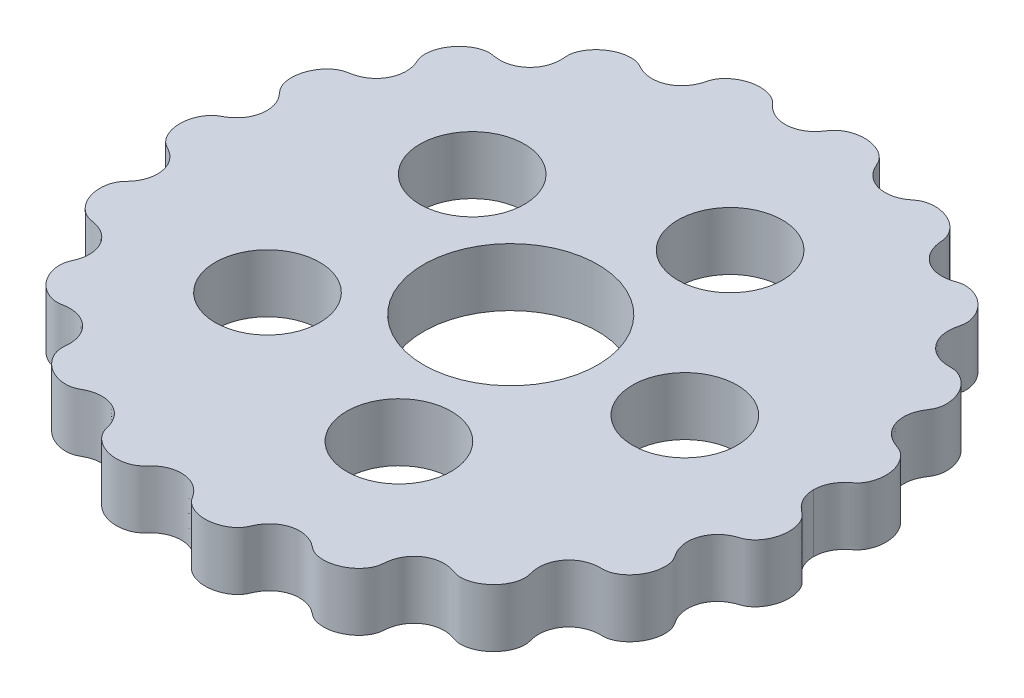
SolidWorks part; units mm, degrees
ref_plane "Front Plane" through (0, 0, 0) normal (0, 0, 1) x (1, 0, 0)
ref_plane "Top Plane" through (0, 0, 0) normal (0, 1, 0) x (1, 0, 0)
ref_plane "Right Plane" through (0, 0, 0) normal (1, 0, 0) x (0, 0, -1)
sketch "Sketch1" plane through (0, 0, 0) normal (0, 1, 0) x (1, 0, 0)
  line L0 (-28.5, 0) -> (26.1, 0) construction
  line L1 (0, 0) -> (-1.2, 0) construction
  line L2 (-1.2, -26.2965) -> (-1.2, 26.2965) construction
  line L3 (0, -27.4748) -> (0, 27.4748) construction
  line L4 (15, 0) -> (16.8, 0)
  line L5 (-1.2, 0) -> (-2.4, 0)
  circle A6 centre (0, 0) radius 7.5
  circle A7 centre (0, 0) radius 15
  circle A8 centre (15, 0) radius 4.5
  circle A9 centre (4.6353, -14.2658) radius 4.5
  circle A10 centre (-12.1353, -8.8168) radius 4.5
  circle A11 centre (-12.1353, 8.8168) radius 4.5
  circle A12 centre (4.6353, 14.2658) radius 4.5
  circle A13 centre (-1.2, 0) radius 30
  circle A14 centre (28.8, 0) radius 2.5
  circle A15 centre (27.3317, -9.2705) radius 2.5
  circle A16 centre (23.0705, -17.6336) radius 2.5
  circle A17 centre (16.4336, -24.2705) radius 2.5
  circle A18 centre (8.0705, -28.5317) radius 2.5
  circle A19 centre (-1.2, -30) radius 2.5
  circle A20 centre (-10.4705, -28.5317) radius 2.5
  circle A21 centre (-18.8336, -24.2705) radius 2.5
  circle A22 centre (-25.4705, -17.6336) radius 2.5
  circle A23 centre (-29.7317, -9.2705) radius 2.5
  circle A24 centre (-31.2, 0) radius 2.5
  circle A25 centre (-29.7317, 9.2705) radius 2.5
  circle A26 centre (-25.4705, 17.6336) radius 2.5
  circle A27 centre (-18.8336, 24.2705) radius 2.5
  circle A28 centre (-10.4705, 28.5317) radius 2.5
  circle A29 centre (-1.2, 30) radius 2.5
  circle A30 centre (8.0705, 28.5317) radius 2.5
  circle A31 centre (16.4336, 24.2705) radius 2.5
  circle A32 centre (23.0705, 17.6336) radius 2.5
  circle A33 centre (27.3317, 9.2705) radius 2.5
  circle A41 centre (-2.4, 0) radius 15
  circle A42 centre (12.6, 0) radius 3.75
  spline S0 degree 4 poles (26.9104, 6.6012) (26.9742, 6.5637) (27.0975, 6.4823) (27.3266, 6.2942) (27.6183, 5.9575) (27.8831, 5.5093) (28.0722, 4.9735) (28.1608, 4.4391) (28.1609, 3.9238) (28.093, 3.5007) (27.9838, 3.1507) (27.8591, 2.8784) (27.741, 2.6778) (27.605, 2.4959) (27.4503, 2.337) (27.2759, 2.2009) (27.1019, 2.0648) (26.9367, 1.9177) (26.7821, 1.7596) (26.65, 1.601) (26.5385, 1.4453) (26.4457, 1.295) (26.3692, 1.1524) (26.3017, 1.0053) (26.2435, 0.8544) (26.1947, 0.7002) (26.1557, 0.5423) (26.1271, 0.3877) (26.1084, 0.2314) (26.0989, 0.0495) (26.0994, -0.0671) (26.1108, -0.2691) (26.1342, -0.4315) (26.1693, -0.6042) (26.2157, -0.7717) (26.2733, -0.9361) (26.3418, -1.0961) (26.4279, -1.2656) (26.5348, -1.4419) (26.6997, -1.6703) (26.9014, -1.8899) (27.1248, -2.087) (27.3628, -2.2652) (27.5417, -2.4229) (27.6968, -2.6125) (27.831, -2.8239) (27.9427, -3.0552) (28.032, -3.3021) (28.1133, -3.6202) (28.1642, -4.0114) (28.1582, -4.4659) (28.0687, -4.972) (27.9224, -5.3919) (27.7522, -5.7264) (27.5792, -5.9861) (27.4226, -6.1811) (27.2087, -6.3966) (26.9704, -6.5815) (26.7043, -6.7144) (26.4261, -6.8021) (26.2084, -6.8853) (25.996, -6.9818) (25.7924, -7.0957) (25.5065, -7.2884) (25.1668, -7.5959) (24.8233, -8.0656) (24.5731, -8.7228) (24.5132, -9.3741) (24.5959, -9.9089) (24.7329, -10.3062) (24.8635, -10.5783) (24.9836, -10.7878) (25.1181, -10.988) (25.2439, -11.1944) (25.336, -11.4251) (25.3995, -11.6707) (25.4343, -11.9282) (25.442, -12.1937) (25.4188, -12.5249) (25.3424, -12.9166) (25.1912, -13.3478) (24.9449, -13.7987) (24.6361, -14.1974) (24.3194, -14.493) (24.0146, -14.7042) (23.7442, -14.8441) (23.522, -14.9308) (23.2952, -14.9909) (23.0662, -15.0181) (22.8362, -15.0154) (22.6065, -15.0188) (22.3771, -15.0374) (22.15, -15.0735) (21.9017, -15.1343) (21.6364, -15.2275) (21.2852, -15.3974) (20.867, -15.6962) (20.4577, -16.1544) (20.1676, -16.7441) (20.0407, -17.3441) (20.0443, -17.8376) (20.1013, -18.2083) (20.1783, -18.5102) (20.2374, -18.7529) (20.2542, -19.0071) (20.2367, -19.2645) (20.1753, -19.5877) (20.0454, -19.9662) (19.8257, -20.3791) (19.5033, -20.7922) (19.1257, -21.1406) (18.7061, -21.4192) (18.3126, -21.5978) (17.9573, -21.7007) (17.6591, -21.7472) (17.425, -21.7593) (17.197, -21.746) (16.9781, -21.7045) (16.7675, -21.6331) (16.5576, -21.5612) (16.3432, -21.5027) (16.1253, -21.4593) (15.7965, -21.4204) (15.3549, -21.428) (14.789, -21.5503) (14.1546, -21.8806) (13.6662, -22.3459) (13.3364, -22.8823) (13.1735, -23.3537) (13.1046, -23.717) (13.0767, -24.0228) (13.0578, -24.2682) (12.9987, -24.5141) (12.9032, -24.7542) (12.7442, -25.0453) (12.499, -25.369) (12.1557, -25.6963) (11.7049, -25.9946) (11.2116, -26.2122) (10.69, -26.3437) (10.2213, -26.3776) (9.8206, -26.3426) (9.499, -26.2667) (9.2556, -26.1771) (9.0298, -26.0566) (8.8316, -25.9026) (8.5839, -25.7111) (8.2645, -25.511) (7.8101, -25.3123) (7.2055, -25.1928) (6.5502, -25.2287) (5.9713, -25.4243) (5.5369, -25.6878) (5.2457, -25.9387) (5.0554, -26.1438) (4.8999, -26.3482) (4.7746, -26.5455) (4.6646, -26.7519) (4.569, -26.9649) (4.4763, -27.1796) (4.3535, -27.3793) (4.2033, -27.5619) (4.0321, -27.728) (3.7953, -27.9145) (3.4825, -28.1028) (3.0896, -28.2688) (2.605, -28.3883) (2.0954, -28.4312) (1.5735, -28.39) (1.1195, -28.2728) (0.7516, -28.1124) (0.4728, -27.9399) (0.2735, -27.7809) (0.1002, -27.6012) (-0.0369, -27.4007) (-0.1676, -27.1967) (-0.3131, -27.0024) (-0.5125, -26.7738) (-0.8252, -26.4899) (-1.2868, -26.2024) (-1.9065, -26.0034) (-2.5994, -25.9754) (-3.1568, -26.101) (-3.5653, -26.2832) (-3.8534, -26.4638) (-4.0409, -26.6046) (-4.2161, -26.7602) (-4.3804, -26.9272) (-4.5356, -27.1027) (-4.708, -27.2621) (-4.9066, -27.3955) (-5.1223, -27.5066) (-5.3531, -27.5948) (-5.5951, -27.6608) (-5.9041, -27.715) (-6.2804, -27.7366) (-6.7242, -27.7014) (-7.2225, -27.58) (-7.6392, -27.4035) (-7.9745, -27.2016) (-8.2316, -27.0015) (-8.4208, -26.8224) (-8.5884, -26.628) (-8.73, -26.4192) (-8.8438, -26.1979) (-8.9181, -25.9651) (-8.9731, -25.7277) (-9.0439, -25.4943) (-9.1531, -25.2096) (-9.3068, -24.9159) (-9.5135, -24.6237) (-9.8398, -24.2849) (-10.2644, -23.9778) (-10.8297, -23.7381) (-11.4105, -23.6609) (-11.8763, -23.6964) (-12.2188, -23.7735) (-12.4447, -23.8451) (-12.6638, -23.9353) (-12.8761, -24.0403) (-13.082, -24.1572) (-13.2986, -24.2543) (-13.5339, -24.3178) (-13.7805, -24.3538) (-14.0358, -24.3616) (-14.2964, -24.3431) (-14.6185, -24.2887) (-14.9949, -24.1775) (-15.4086, -23.9883) (-15.8372, -23.7006) (-16.1649, -23.3939) (-16.4043, -23.0978) (-16.5733, -22.8298) (-16.6877, -22.6036) (-16.7767, -22.3723) (-16.8377, -22.1385) (-16.8702, -21.9045) (-16.8664, -21.6745) (-16.8432, -21.4462) (-16.8326, -21.2169) (-16.8373, -20.9873) (-16.8603, -20.7588) (-16.9233, -20.4192) (-17.0718, -19.9806) (-17.369, -19.4772) (-17.8749, -18.9885) (-18.448, -18.6772) (-19.0275, -18.5257) (-19.5101, -18.5038) (-19.8766, -18.5383) (-20.1776, -18.5934) (-20.4214, -18.6224) (-20.6712, -18.6091) (-20.9209, -18.565) (-21.1679, -18.4906) (-21.4096, -18.39) (-21.6982, -18.2354) (-22.0201, -18.0093) (-22.351, -17.6983) (-22.6637, -17.2907) (-22.9048, -16.8434) (-23.0478, -16.4273) (-23.1163, -16.0571) (-23.132, -15.7508) (-23.1187, -15.5137) (-23.0797, -15.2858) (-23.0107, -15.072) (-22.918, -14.8679) (-22.8318, -14.6612) (-22.759, -14.4492) (-22.7023, -14.2323) (-22.658, -13.9823) (-22.6359, -13.6994) (-22.6507, -13.3001) (-22.7619, -12.7838) (-23.0293, -12.2149) (-23.4676, -11.712) (-23.9234, -11.3981) (-24.3155, -11.223) (-24.6094, -11.1314) (-24.8495, -11.076) (-25.0926, -11.0387) (-25.3345, -10.9908) (-25.5693, -10.9005) (-25.7937, -10.7797) (-26.006, -10.6307) (-26.2044, -10.4578) (-26.4303, -10.2184) (-26.6648, -9.8998) (-26.879, -9.4996) (-27.0444, -9.0157) (-27.13, -8.5201) (-27.1345, -8.0871) (-27.0849, -7.7198) (-27.006, -7.4259) (-26.9204, -7.2033) (-26.8122, -6.9952) (-26.6786, -6.8073) (-26.5213, -6.6394) (-26.3676, -6.4686) (-26.2255, -6.2877) (-26.0974, -6.0966) (-25.9747, -5.8762) (-25.8647, -5.6245) (-25.7524, -5.2647) (-25.6818, -4.7626) (-25.731, -4.1469) (-25.9619, -3.524) (-26.3213, -3.0106) (-26.6902, -2.673) (-27.001, -2.4627) (-27.2749, -2.314) (-27.4942, -2.1942) (-27.6938, -2.0358) (-27.8724, -1.8494) (-28.0299, -1.6395) (-28.1658, -1.4106) (-28.2784, -1.1691) (-28.3569, -0.9499) (-28.4099, -0.7574) (-28.4448, -0.5945) (-28.4671, -0.4646) (-28.4838, -0.3341) (-28.4949, -0.1942) (-28.5004, -0.0525) (-28.5005, 0.0456) (-28.4955, 0.1802) (-28.4857, 0.3127) (-28.4674, 0.4669) (-28.4356, 0.6491) (-28.3841, 0.8627) (-28.3055, 1.0987) (-28.2068, 1.3282) (-28.0876, 1.5473) (-27.9509, 1.7495) (-27.7973, 1.9316) (-27.6281, 2.0918) (-27.4431, 2.2241) (-27.2427, 2.3305) (-27.0445, 2.4404) (-26.8537, 2.5632) (-26.6725, 2.6998) (-26.4853, 2.8663) (-26.2987, 3.0673) (-26.073, 3.3712) (-25.8526, 3.7999) (-25.7033, 4.3429) (-25.6908, 4.9349) (-25.7972, 5.4631) (-25.983, 5.9142) (-26.1842, 6.2409) (-26.3898, 6.4964) (-26.5384, 6.6564) (-26.611, 6.7378) (-26.647, 6.7788) knots 0 0 0 0 0 0.002514 0.005029 0.010058 0.015086 0.020115 0.024264 0.028413 0.032562 0.034636 0.03671 0.038591 0.040472 0.042353 0.044234 0.046115 0.047995 0.049876 0.051757 0.053134 0.05451 0.055887 0.057263 0.05864 0.060016 0.061393 0.06277 0.064064 0.065358 0.066839 0.06832 0.069801 0.071282 0.072763 0.074244 0.075725 0.077206 0.079231 0.081256 0.085305 0.087329 0.089354 0.091379 0.093403 0.095635 0.097867 0.100099 0.102331 0.106795 0.111259 0.115506 0.119752 0.121875 0.123998 0.126122 0.128245 0.132212 0.134196 0.13618 0.138163 0.140147 0.142131 0.144114 0.149889 0.155664 0.161717 0.167769 0.171876 0.173929 0.175982 0.178036 0.180089 0.182142 0.184196 0.186453 0.18871 0.190968 0.193225 0.19774 0.202255 0.20645 0.210645 0.21484 0.216937 0.219035 0.220991 0.222947 0.224903 0.226859 0.228815 0.230771 0.232727 0.234683 0.237505 0.240328 0.245974 0.252074 0.258174 0.262418 0.266663 0.268785 0.270907 0.27303 0.275152 0.277414 0.279676 0.284201 0.288725 0.29325 0.297435 0.301619 0.305804 0.307896 0.309989 0.311878 0.313768 0.315658 0.317547 0.319437 0.321327 0.323216 0.325106 0.330698 0.336289 0.342722 0.349154 0.353338 0.357522 0.359614 0.361706 0.363798 0.365889 0.368184 0.370478 0.375067 0.379656 0.384245 0.388791 0.393338 0.397884 0.400157 0.40243 0.404563 0.406695 0.408827 0.41096 0.415225 0.41949 0.425619 0.431749 0.437282 0.440049 0.442815 0.444803 0.446791 0.448779 0.450767 0.452755 0.454743 0.456731 0.458718 0.460784 0.462849 0.466979 0.47111 0.47524 0.479777 0.484314 0.488851 0.491119 0.493388 0.495451 0.497514 0.499578 0.501641 0.503704 0.505768 0.509894 0.515977 0.52206 0.527644 0.533228 0.535221 0.537214 0.539208 0.541201 0.543194 0.545187 0.54718 0.549173 0.551306 0.553439 0.555572 0.557704 0.56197 0.566236 0.570665 0.575094 0.577308 0.579523 0.581737 0.583952 0.586026 0.5881 0.590174 0.592248 0.594322 0.596397 0.600545 0.6035 0.606456 0.612367 0.618261 0.624154 0.626169 0.628184 0.630198 0.632213 0.634228 0.636243 0.638257 0.640272 0.642493 0.644714 0.646935 0.649156 0.653597 0.658039 0.662348 0.666657 0.668812 0.670967 0.673121 0.675276 0.677229 0.679181 0.681134 0.683087 0.68504 0.686993 0.688946 0.690899 0.696786 0.702673 0.708614 0.714556 0.718724 0.722892 0.724976 0.72706 0.729144 0.731229 0.733454 0.73568 0.737906 0.740131 0.744583 0.749034 0.753293 0.757552 0.76181 0.76394 0.766069 0.767975 0.769882 0.771788 0.773694 0.775601 0.777507 0.779413 0.78132 0.784235 0.787151 0.792981 0.799177 0.805373 0.809561 0.811656 0.81375 0.815844 0.817939 0.820033 0.822127 0.824365 0.826603 0.828841 0.831079 0.835554 0.84003 0.844223 0.848415 0.852608 0.854705 0.856801 0.858757 0.860713 0.862669 0.864625 0.866581 0.868537 0.870493 0.87245 0.875161 0.877872 0.883295 0.889615 0.895936 0.900182 0.904428 0.906551 0.908674 0.910797 0.912919 0.915183 0.917446 0.919709 0.921972 0.924235 0.925367 0.926498 0.92763 0.928762 0.929893 0.931025 0.932085 0.933146 0.934206 0.935267 0.937388 0.939509 0.94163 0.943751 0.945872 0.947993 0.949922 0.951852 0.953781 0.95571 0.95764 0.959569 0.961498 0.963428 0.966159 0.968891 0.974355 0.979745 0.985135 0.988851 0.992568 0.996284 0.998142 1 1 1 1 1 construction
  spline S1 degree 4 poles (26.1, 0) (26.1, -0.0377) (26.102, -0.1127) (26.1108, -0.2691) (26.1342, -0.4315) (26.1693, -0.6042) (26.2157, -0.7717) (26.2733, -0.9361) (26.3418, -1.0961) (26.4279, -1.2656) (26.5348, -1.4419) (26.6997, -1.6703) (26.9014, -1.8899) (27.1248, -2.087) (27.3628, -2.2652) (27.5417, -2.4229) (27.6968, -2.6125) (27.831, -2.8239) (27.9427, -3.0552) (28.032, -3.3021) (28.1133, -3.6202) (28.1642, -4.0114) (28.1582, -4.4659) (28.0687, -4.972) (27.9224, -5.3919) (27.7522, -5.7264) (27.5792, -5.9861) (27.4226, -6.1811) (27.2087, -6.3966) (26.9704, -6.5815) (26.7043, -6.7144) (26.4261, -6.8021) (26.2084, -6.8853) (25.996, -6.9818) (25.7924, -7.0957) (25.5065, -7.2884) (25.1668, -7.5959) (24.8233, -8.0656) (24.5731, -8.7228) (24.5132, -9.3741) (24.5959, -9.9089) (24.7329, -10.3062) (24.8635, -10.5783) (24.9836, -10.7878) (25.1181, -10.988) (25.2439, -11.1944) (25.336, -11.4251) (25.3995, -11.6707) (25.4343, -11.9282) (25.442, -12.1937) (25.4188, -12.5249) (25.3424, -12.9166) (25.1912, -13.3478) (24.9449, -13.7987) (24.6361, -14.1974) (24.3194, -14.493) (24.0146, -14.7042) (23.7442, -14.8441) (23.522, -14.9308) (23.2952, -14.9909) (23.0662, -15.0181) (22.8362, -15.0154) (22.6065, -15.0188) (22.3771, -15.0374) (22.15, -15.0735) (21.9017, -15.1343) (21.6364, -15.2275) (21.2852, -15.3974) (20.867, -15.6962) (20.4577, -16.1544) (20.1676, -16.7441) (20.0407, -17.3441) (20.0443, -17.8376) (20.1013, -18.2083) (20.1783, -18.5102) (20.2374, -18.7529) (20.2542, -19.0071) (20.2367, -19.2645) (20.1753, -19.5877) (20.0454, -19.9662) (19.8257, -20.3791) (19.5033, -20.7922) (19.1257, -21.1406) (18.7061, -21.4192) (18.3126, -21.5978) (17.9573, -21.7007) (17.6591, -21.7472) (17.425, -21.7593) (17.197, -21.746) (16.9781, -21.7045) (16.7675, -21.6331) (16.5576, -21.5612) (16.3432, -21.5027) (16.1253, -21.4593) (15.7965, -21.4204) (15.3549, -21.428) (14.789, -21.5503) (14.1546, -21.8806) (13.6662, -22.3459) (13.3364, -22.8823) (13.1735, -23.3537) (13.1046, -23.717) (13.0767, -24.0228) (13.0578, -24.2682) (12.9987, -24.5141) (12.9032, -24.7542) (12.7442, -25.0453) (12.499, -25.369) (12.1557, -25.6963) (11.7049, -25.9946) (11.2116, -26.2122) (10.69, -26.3437) (10.2213, -26.3776) (9.8206, -26.3426) (9.499, -26.2667) (9.2556, -26.1771) (9.0298, -26.0566) (8.8316, -25.9026) (8.5839, -25.7111) (8.2645, -25.511) (7.8101, -25.3123) (7.2055, -25.1928) (6.5502, -25.2287) (5.9713, -25.4243) (5.5369, -25.6878) (5.2457, -25.9387) (5.0554, -26.1438) (4.8999, -26.3482) (4.7746, -26.5455) (4.6646, -26.7519) (4.569, -26.9649) (4.4763, -27.1796) (4.3535, -27.3793) (4.2033, -27.5619) (4.0321, -27.728) (3.7953, -27.9145) (3.4825, -28.1028) (3.0896, -28.2688) (2.605, -28.3883) (2.0954, -28.4312) (1.5735, -28.39) (1.1195, -28.2728) (0.7516, -28.1124) (0.4728, -27.9399) (0.2735, -27.7809) (0.1002, -27.6012) (-0.0369, -27.4007) (-0.1676, -27.1967) (-0.3131, -27.0024) (-0.5125, -26.7738) (-0.8252, -26.4899) (-1.2868, -26.2024) (-1.9065, -26.0034) (-2.5994, -25.9754) (-3.1568, -26.101) (-3.5653, -26.2832) (-3.8534, -26.4638) (-4.0409, -26.6046) (-4.2161, -26.7602) (-4.3804, -26.9272) (-4.5356, -27.1027) (-4.708, -27.2621) (-4.9066, -27.3955) (-5.1223, -27.5066) (-5.3531, -27.5948) (-5.5951, -27.6608) (-5.9041, -27.715) (-6.2804, -27.7366) (-6.7242, -27.7014) (-7.2225, -27.58) (-7.6392, -27.4035) (-7.9745, -27.2016) (-8.2316, -27.0015) (-8.4208, -26.8224) (-8.5884, -26.628) (-8.73, -26.4192) (-8.8438, -26.1979) (-8.9181, -25.9651) (-8.9731, -25.7277) (-9.0439, -25.4943) (-9.1531, -25.2096) (-9.3068, -24.9159) (-9.5135, -24.6237) (-9.8398, -24.2849) (-10.2644, -23.9778) (-10.8297, -23.7381) (-11.4105, -23.6609) (-11.8763, -23.6964) (-12.2188, -23.7735) (-12.4447, -23.8451) (-12.6638, -23.9353) (-12.8761, -24.0403) (-13.082, -24.1572) (-13.2986, -24.2543) (-13.5339, -24.3178) (-13.7805, -24.3538) (-14.0358, -24.3616) (-14.2964, -24.3431) (-14.6185, -24.2887) (-14.9949, -24.1775) (-15.4086, -23.9883) (-15.8372, -23.7006) (-16.1649, -23.3939) (-16.4043, -23.0978) (-16.5733, -22.8298) (-16.6877, -22.6036) (-16.7767, -22.3723) (-16.8377, -22.1385) (-16.8702, -21.9045) (-16.8664, -21.6745) (-16.8432, -21.4462) (-16.8326, -21.2169) (-16.8373, -20.9873) (-16.8603, -20.7588) (-16.9233, -20.4192) (-17.0718, -19.9806) (-17.369, -19.4772) (-17.8749, -18.9885) (-18.448, -18.6772) (-19.0275, -18.5257) (-19.5101, -18.5038) (-19.8766, -18.5383) (-20.1776, -18.5934) (-20.4214, -18.6224) (-20.6712, -18.6091) (-20.9209, -18.565) (-21.1679, -18.4906) (-21.4096, -18.39) (-21.6982, -18.2354) (-22.0201, -18.0093) (-22.351, -17.6983) (-22.6637, -17.2907) (-22.9048, -16.8434) (-23.0478, -16.4273) (-23.1163, -16.0571) (-23.132, -15.7508) (-23.1187, -15.5137) (-23.0797, -15.2858) (-23.0107, -15.072) (-22.918, -14.8679) (-22.8318, -14.6612) (-22.759, -14.4492) (-22.7023, -14.2323) (-22.658, -13.9823) (-22.6359, -13.6994) (-22.6507, -13.3001) (-22.7619, -12.7838) (-23.0293, -12.2149) (-23.4676, -11.712) (-23.9234, -11.3981) (-24.3155, -11.223) (-24.6094, -11.1314) (-24.8495, -11.076) (-25.0926, -11.0387) (-25.3345, -10.9908) (-25.5693, -10.9005) (-25.7937, -10.7797) (-26.006, -10.6307) (-26.2044, -10.4578) (-26.4303, -10.2184) (-26.6648, -9.8998) (-26.879, -9.4996) (-27.0444, -9.0157) (-27.13, -8.5201) (-27.1345, -8.0871) (-27.0849, -7.7198) (-27.006, -7.4259) (-26.9204, -7.2033) (-26.8122, -6.9952) (-26.6786, -6.8073) (-26.5213, -6.6394) (-26.3676, -6.4686) (-26.2255, -6.2877) (-26.0974, -6.0966) (-25.9747, -5.8762) (-25.8647, -5.6245) (-25.7524, -5.2647) (-25.6818, -4.7626) (-25.731, -4.1469) (-25.9619, -3.524) (-26.3213, -3.0106) (-26.6902, -2.673) (-27.001, -2.4627) (-27.2749, -2.314) (-27.4942, -2.1942) (-27.6938, -2.0358) (-27.8724, -1.8494) (-28.0299, -1.6395) (-28.1658, -1.4106) (-28.2784, -1.1691) (-28.3569, -0.9499) (-28.4099, -0.7574) (-28.4448, -0.5945) (-28.4671, -0.4646) (-28.4838, -0.3341) (-28.4949, -0.1942) (-28.4991, -0.0862) (-28.5, -0.0288) (-28.5, 0) knots 0.065358 0.065358 0.065358 0.065358 0.065358 0.066839 0.06832 0.069801 0.071282 0.072763 0.074244 0.075725 0.077206 0.079231 0.081256 0.085305 0.087329 0.089354 0.091379 0.093403 0.095635 0.097867 0.100099 0.102331 0.106795 0.111259 0.115506 0.119752 0.121875 0.123998 0.126122 0.128245 0.132212 0.134196 0.13618 0.138163 0.140147 0.142131 0.144114 0.149889 0.155664 0.161717 0.167769 0.171876 0.173929 0.175982 0.178036 0.180089 0.182142 0.184196 0.186453 0.18871 0.190968 0.193225 0.19774 0.202255 0.20645 0.210645 0.21484 0.216937 0.219035 0.220991 0.222947 0.224903 0.226859 0.228815 0.230771 0.232727 0.234683 0.237505 0.240328 0.245974 0.252074 0.258174 0.262418 0.266663 0.268785 0.270907 0.27303 0.275152 0.277414 0.279676 0.284201 0.288725 0.29325 0.297435 0.301619 0.305804 0.307896 0.309989 0.311878 0.313768 0.315658 0.317547 0.319437 0.321327 0.323216 0.325106 0.330698 0.336289 0.342722 0.349154 0.353338 0.357522 0.359614 0.361706 0.363798 0.365889 0.368184 0.370478 0.375067 0.379656 0.384245 0.388791 0.393338 0.397884 0.400157 0.40243 0.404563 0.406695 0.408827 0.41096 0.415225 0.41949 0.425619 0.431749 0.437282 0.440049 0.442815 0.444803 0.446791 0.448779 0.450767 0.452755 0.454743 0.456731 0.458718 0.460784 0.462849 0.466979 0.47111 0.47524 0.479777 0.484314 0.488851 0.491119 0.493388 0.495451 0.497514 0.499578 0.501641 0.503704 0.505768 0.509894 0.515977 0.52206 0.527644 0.533228 0.535221 0.537214 0.539208 0.541201 0.543194 0.545187 0.54718 0.549173 0.551306 0.553439 0.555572 0.557704 0.56197 0.566236 0.570665 0.575094 0.577308 0.579523 0.581737 0.583952 0.586026 0.5881 0.590174 0.592248 0.594322 0.596397 0.600545 0.6035 0.606456 0.612367 0.618261 0.624154 0.626169 0.628184 0.630198 0.632213 0.634228 0.636243 0.638257 0.640272 0.642493 0.644714 0.646935 0.649156 0.653597 0.658039 0.662348 0.666657 0.668812 0.670967 0.673121 0.675276 0.677229 0.679181 0.681134 0.683087 0.68504 0.686993 0.688946 0.690899 0.696786 0.702673 0.708614 0.714556 0.718724 0.722892 0.724976 0.72706 0.729144 0.731229 0.733454 0.73568 0.737906 0.740131 0.744583 0.749034 0.753293 0.757552 0.76181 0.76394 0.766069 0.767975 0.769882 0.771788 0.773694 0.775601 0.777507 0.779413 0.78132 0.784235 0.787151 0.792981 0.799177 0.805373 0.809561 0.811656 0.81375 0.815844 0.817939 0.820033 0.822127 0.824365 0.826603 0.828841 0.831079 0.835554 0.84003 0.844223 0.848415 0.852608 0.854705 0.856801 0.858757 0.860713 0.862669 0.864625 0.866581 0.868537 0.870493 0.87245 0.875161 0.877872 0.883295 0.889615 0.895936 0.900182 0.904428 0.906551 0.908674 0.910797 0.912919 0.915183 0.917446 0.919709 0.921972 0.924235 0.925367 0.926498 0.92763 0.928762 0.929893 0.931025 0.931025 0.931025 0.931025 0.931025
  spline S2 degree 4 poles (26.1, 0) (26.1, 0.0376) (26.102, 0.1124) (26.1108, 0.2685) (26.1342, 0.4303) (26.1693, 0.6027) (26.2157, 0.7697) (26.2733, 0.9336) (26.3417, 1.0932) (26.4279, 1.2622) (26.5346, 1.438) (26.6647, 1.6175) (26.8202, 1.7972) (26.9901, 1.9633) (27.1709, 2.1172) (27.3596, 2.2614) (27.5347, 2.4225) (27.6873, 2.6133) (27.8194, 2.8254) (27.9294, 3.0568) (28.0174, 3.3035) (28.0973, 3.6212) (28.1472, 4.0116) (28.1407, 4.4663) (28.0507, 4.9735) (27.8829, 5.455) (27.6715, 5.843) (27.4436, 6.1449) (27.2267, 6.3648) (27.0409, 6.5166) (26.8436, 6.6432) (26.6359, 6.7382) (26.4199, 6.8111) (26.2069, 6.8919) (25.9995, 6.9866) (25.7999, 7.097) (25.5146, 7.2869) (25.172, 7.593) (24.8251, 8.0632) (24.573, 8.723) (24.5135, 9.3751) (24.5967, 9.9085) (24.7339, 10.3046) (24.8642, 10.5762) (24.9838, 10.7853) (25.1166, 10.986) (25.2378, 11.1945) (25.3267, 11.4258) (25.3878, 11.6713) (25.4209, 11.9285) (25.4273, 12.1933) (25.4029, 12.5237) (25.3257, 12.9142) (25.174, 13.3453) (24.9269, 13.7973) (24.6164, 14.1978) (24.297, 14.4955) (23.9896, 14.7081) (23.7185, 14.8479) (23.4979, 14.934) (23.2747, 14.9937) (23.0513, 15.0227) (22.8265, 15.0238) (22.6021, 15.0278) (22.378, 15.046) (22.1559, 15.0804) (21.8286, 15.1585) (21.4093, 15.3223) (20.9247, 15.6352) (20.4568, 16.1578) (20.1669, 16.7485) (20.041, 17.3471) (20.0453, 17.8394) (20.1023, 18.2092) (20.1778, 18.5107) (20.2318, 18.7541) (20.2449, 19.0078) (20.2252, 19.2644) (20.1746, 19.5212) (20.0962, 19.7748) (19.9675, 20.0808) (19.7692, 20.427) (19.4884, 20.786) (19.1123, 21.133) (18.6951, 21.411) (18.3044, 21.5899) (17.9516, 21.6944) (17.5971, 21.7522) (17.3027, 21.7613) (17.0135, 21.7242) (16.7419, 21.6352) (16.5255, 21.5634) (16.3045, 21.5051) (16.08, 21.4631) (15.8308, 21.4372) (15.5583, 21.4348) (15.1861, 21.4722) (14.6961, 21.6037) (14.1458, 21.8923) (13.6634, 22.3528) (13.3351, 22.8883) (13.1733, 23.3588) (13.1047, 23.7212) (13.0759, 24.0263) (13.0525, 24.2707) (12.9895, 24.515) (12.8921, 24.7535) (12.7313, 25.0427) (12.4854, 25.3645) (12.1419, 25.6899) (11.6909, 25.9876) (11.1964, 26.2054) (10.6723, 26.3373) (10.2003, 26.3711) (9.7968, 26.3356) (9.4748, 26.2593) (9.233, 26.1706) (9.01, 26.0529) (8.8137, 25.9055) (8.5704, 25.7195) (8.2582, 25.5237) (7.8094, 25.325) (7.2073, 25.202) (6.5461, 25.2353) (5.8772, 25.4622) (5.3986, 25.786) (5.085, 26.1055) (4.8853, 26.3742) (4.7666, 26.5637) (4.6617, 26.7612) (4.5693, 26.9645) (4.4773, 27.1684) (4.3594, 27.359) (4.2144, 27.5373) (4.0466, 27.7027) (3.8098, 27.8925) (3.4925, 28.0862) (3.093, 28.2569) (2.6024, 28.3789) (2.0891, 28.4226) (1.566, 28.382) (1.1127, 28.2662) (0.7451, 28.1078) (0.4658, 27.9376) (0.2655, 27.7808) (0.0903, 27.6039) (-0.0506, 27.4068) (-0.1822, 27.204) (-0.3275, 27.0102) (-0.5264, 26.7821) (-0.838, 26.4986) (-1.2981, 26.2111) (-1.9184, 26.0114) (-2.6145, 25.984) (-3.1735, 26.1125) (-3.582, 26.2979) (-3.8673, 26.4791) (-4.0499, 26.6174) (-4.2212, 26.7695) (-4.3819, 26.9324) (-4.5359, 27.1018) (-4.7063, 27.2554) (-4.9021, 27.3863) (-5.1165, 27.4966) (-5.3472, 27.5851) (-5.5911, 27.6519) (-5.9024, 27.7067) (-6.2817, 27.7289) (-6.73, 27.6934) (-7.2343, 27.5702) (-7.6563, 27.3905) (-7.9967, 27.1843) (-8.2563, 26.9795) (-8.4483, 26.7967) (-8.6511, 26.5554) (-8.817, 26.2938) (-8.9134, 26.0392) (-8.9701, 25.8124) (-9.0327, 25.5873) (-9.1257, 25.31) (-9.3159, 24.91) (-9.6747, 24.4361) (-10.1835, 24.0258) (-10.8362, 23.7471) (-11.4204, 23.6699) (-11.885, 23.7058) (-12.2267, 23.7831) (-12.452, 23.8548) (-12.6708, 23.9446) (-12.8827, 24.0491) (-13.0896, 24.1633) (-13.3076, 24.2559) (-13.543, 24.3166) (-13.7894, 24.3504) (-14.0442, 24.3567) (-14.3041, 24.337) (-14.6252, 24.2816) (-15.0005, 24.1698) (-15.413, 23.9806) (-15.8407, 23.6936) (-16.2143, 23.3448) (-16.485, 22.9926) (-16.6692, 22.6601) (-16.7825, 22.3711) (-16.8455, 22.1383) (-16.8805, 21.9053) (-16.8813, 21.6757) (-16.8608, 21.4476) (-16.8506, 21.2188) (-16.8554, 20.9897) (-16.8782, 20.7616) (-16.9407, 20.4228) (-17.0884, 19.9851) (-17.3858, 19.4807) (-17.8945, 18.9905) (-18.4699, 18.6811) (-18.9904, 18.5487) (-19.4065, 18.5188) (-19.706, 18.5311) (-19.9442, 18.558) (-20.1802, 18.5992) (-20.4191, 18.6236) (-20.6652, 18.6099) (-20.9131, 18.5657) (-21.1602, 18.4916) (-21.4036, 18.3903) (-21.6943, 18.2349) (-22.0185, 18.0074) (-22.3518, 17.6944) (-22.6668, 17.2838) (-22.9095, 16.8332) (-23.0533, 16.4139) (-23.122, 16.0408) (-23.1375, 15.7333) (-23.1242, 15.4968) (-23.0858, 15.2707) (-23.0198, 15.0593) (-22.9309, 14.8568) (-22.847, 14.6525) (-22.7758, 14.4431) (-22.7201, 14.2291) (-22.6612, 13.8972) (-22.6444, 13.4427) (-22.7419, 12.8653) (-23.0456, 12.2192) (-23.4424, 11.7647) (-23.8363, 11.4753) (-24.161, 11.3062) (-24.3884, 11.2127) (-24.6231, 11.1398) (-24.8625, 11.0843) (-25.1048, 11.0455) (-25.3451, 10.9926) (-25.5781, 10.8996) (-25.8009, 10.7771) (-26.0117, 10.6271) (-26.2088, 10.4536) (-26.4333, 10.2139) (-26.6665, 9.8956) (-26.8796, 9.4961) (-27.0447, 9.0134) (-27.1306, 8.5189) (-27.1361, 8.0869) (-27.0881, 7.7202) (-27.0111, 7.4265) (-26.9274, 7.2037) (-26.8215, 6.9951) (-26.6914, 6.8052) (-26.5372, 6.635) (-26.3844, 6.4641) (-26.2428, 6.2834) (-26.1149, 6.0928) (-25.9923, 5.8728) (-25.8823, 5.6218) (-25.77, 5.2629) (-25.699, 4.7597) (-25.7493, 4.1408) (-25.9834, 3.518) (-26.345, 3.0082) (-26.7118, 2.6756) (-27.016, 2.4701) (-27.2831, 2.3232) (-27.4957, 2.2024) (-27.6915, 2.0453) (-27.8687, 1.86) (-28.0262, 1.6502) (-28.1632, 1.4198) (-28.2767, 1.1768) (-28.3557, 0.9562) (-28.4092, 0.7624) (-28.4443, 0.5985) (-28.4668, 0.4676) (-28.4836, 0.3363) (-28.4949, 0.1958) (-28.4991, 0.0868) (-28.5, 0.029) (-28.5, 0) knots 0.065429 0.065429 0.065429 0.065429 0.065429 0.066909 0.06839 0.06987 0.071351 0.072832 0.074312 0.075793 0.077274 0.079299 0.081323 0.083348 0.085373 0.087398 0.089423 0.091448 0.093473 0.095705 0.097936 0.100168 0.1024 0.106864 0.111328 0.115615 0.119903 0.124191 0.126335 0.128478 0.130422 0.132365 0.134309 0.136252 0.138195 0.140139 0.142082 0.144026 0.149879 0.155733 0.161783 0.167834 0.17194 0.173994 0.176047 0.1781 0.180154 0.182207 0.184261 0.186518 0.188775 0.191032 0.193289 0.197803 0.202317 0.206554 0.210791 0.215028 0.217147 0.219265 0.221181 0.223096 0.225012 0.226928 0.228843 0.230759 0.232675 0.23459 0.240315 0.24604 0.252138 0.258236 0.26248 0.266724 0.268846 0.270968 0.273091 0.275213 0.277474 0.279736 0.281998 0.28426 0.288783 0.293307 0.297478 0.30165 0.305822 0.307907 0.309993 0.313887 0.315834 0.317781 0.319728 0.321675 0.323622 0.325569 0.328265 0.330961 0.336353 0.342782 0.349211 0.353395 0.357579 0.35967 0.361762 0.363854 0.365946 0.36824 0.370534 0.375121 0.379709 0.384296 0.388885 0.393473 0.398062 0.400356 0.40265 0.404741 0.406832 0.408922 0.411013 0.415194 0.419375 0.425582 0.43179 0.437484 0.443178 0.445084 0.44699 0.448896 0.450802 0.452707 0.454613 0.456519 0.458425 0.460533 0.46264 0.466855 0.471071 0.475286 0.479822 0.484358 0.488895 0.491163 0.493431 0.495494 0.497557 0.499621 0.501684 0.503747 0.505811 0.509937 0.516018 0.522099 0.527761 0.533424 0.535376 0.537328 0.539281 0.541233 0.543185 0.545137 0.547089 0.549041 0.551195 0.55335 0.555504 0.557658 0.561967 0.566275 0.570786 0.575296 0.577551 0.579806 0.582061 0.584316 0.588304 0.590297 0.591294 0.592291 0.596278 0.600266 0.606335 0.612404 0.618295 0.624187 0.626202 0.628218 0.630233 0.632248 0.634263 0.636278 0.638293 0.640308 0.642529 0.64475 0.646971 0.649191 0.653633 0.658074 0.662384 0.666693 0.671002 0.673157 0.675311 0.677265 0.679218 0.681171 0.683124 0.685077 0.68703 0.688983 0.690936 0.696822 0.702707 0.708727 0.714747 0.718834 0.720878 0.722922 0.724965 0.727009 0.729053 0.731096 0.733342 0.735588 0.737834 0.74008 0.744572 0.749064 0.753364 0.757665 0.761965 0.764115 0.766265 0.76815 0.770035 0.771919 0.773804 0.775689 0.777574 0.779458 0.781343 0.787178 0.793013 0.799206 0.805399 0.807494 0.809588 0.811682 0.813777 0.815871 0.817965 0.82006 0.822154 0.824391 0.826629 0.828866 0.831104 0.835579 0.840053 0.844247 0.84844 0.852634 0.854731 0.856827 0.858784 0.86074 0.862697 0.864654 0.86661 0.868567 0.870523 0.87248 0.875191 0.877902 0.883324 0.889723 0.896121 0.900285 0.904449 0.906531 0.908613 0.910695 0.912776 0.91506 0.917343 0.919626 0.92191 0.924193 0.925335 0.926476 0.927618 0.92876 0.929901 0.931043 0.931043 0.931043 0.931043 0.931043
  spline S3 degree 4 poles (-28.5, 0) (-28.5, -0.0377) (-28.502, -0.1127) (-28.5108, -0.2691) (-28.5342, -0.4315) (-28.5693, -0.6042) (-28.6157, -0.7717) (-28.6733, -0.9361) (-28.7418, -1.0961) (-28.8279, -1.2656) (-28.9348, -1.4419) (-29.0997, -1.6703) (-29.3014, -1.8899) (-29.5248, -2.087) (-29.7628, -2.2652) (-29.9417, -2.4229) (-30.0968, -2.6125) (-30.231, -2.8239) (-30.3427, -3.0552) (-30.432, -3.3021) (-30.5133, -3.6202) (-30.5642, -4.0114) (-30.5582, -4.4659) (-30.4687, -4.972) (-30.3224, -5.3919) (-30.1522, -5.7264) (-29.9792, -5.9861) (-29.8226, -6.1811) (-29.6087, -6.3966) (-29.3704, -6.5815) (-29.1043, -6.7144) (-28.8261, -6.8021) (-28.6084, -6.8853) (-28.396, -6.9818) (-28.1924, -7.0957) (-27.9065, -7.2884) (-27.5668, -7.5959) (-27.2233, -8.0656) (-26.9731, -8.7228) (-26.9132, -9.3741) (-26.9959, -9.9089) (-27.1329, -10.3062) (-27.2635, -10.5783) (-27.3836, -10.7878) (-27.5181, -10.988) (-27.6439, -11.1944) (-27.736, -11.4251) (-27.7995, -11.6707) (-27.8343, -11.9282) (-27.842, -12.1937) (-27.8188, -12.5249) (-27.7424, -12.9166) (-27.5912, -13.3478) (-27.3449, -13.7987) (-27.0361, -14.1974) (-26.7194, -14.493) (-26.4146, -14.7042) (-26.1442, -14.8441) (-25.922, -14.9308) (-25.6952, -14.9909) (-25.4662, -15.0181) (-25.2362, -15.0154) (-25.0065, -15.0188) (-24.7771, -15.0374) (-24.55, -15.0735) (-24.3017, -15.1343) (-24.0364, -15.2275) (-23.6852, -15.3974) (-23.267, -15.6962) (-22.8577, -16.1544) (-22.5676, -16.7441) (-22.4407, -17.3441) (-22.4443, -17.8376) (-22.5013, -18.2083) (-22.5783, -18.5102) (-22.6374, -18.7529) (-22.6542, -19.0071) (-22.6367, -19.2645) (-22.5753, -19.5877) (-22.4454, -19.9662) (-22.2257, -20.3791) (-21.9033, -20.7922) (-21.5257, -21.1406) (-21.1061, -21.4192) (-20.7126, -21.5978) (-20.3573, -21.7007) (-20.0591, -21.7472) (-19.825, -21.7593) (-19.597, -21.746) (-19.3781, -21.7045) (-19.1675, -21.6331) (-18.9576, -21.5612) (-18.7432, -21.5027) (-18.5253, -21.4593) (-18.1965, -21.4204) (-17.7549, -21.428) (-17.189, -21.5503) (-16.5546, -21.8806) (-16.0662, -22.3459) (-15.7364, -22.8823) (-15.5735, -23.3537) (-15.5046, -23.717) (-15.4767, -24.0228) (-15.4578, -24.2682) (-15.3987, -24.5141) (-15.3032, -24.7542) (-15.1442, -25.0453) (-14.899, -25.369) (-14.5557, -25.6963) (-14.1049, -25.9946) (-13.6116, -26.2122) (-13.09, -26.3437) (-12.6213, -26.3776) (-12.2206, -26.3426) (-11.899, -26.2667) (-11.6556, -26.1771) (-11.4298, -26.0566) (-11.2316, -25.9026) (-10.9839, -25.7111) (-10.6645, -25.511) (-10.2101, -25.3123) (-9.6055, -25.1928) (-8.9502, -25.2287) (-8.3713, -25.4243) (-7.9369, -25.6878) (-7.6457, -25.9387) (-7.4554, -26.1438) (-7.2999, -26.3482) (-7.1746, -26.5455) (-7.0646, -26.7519) (-6.969, -26.9649) (-6.8763, -27.1796) (-6.7535, -27.3793) (-6.6033, -27.5619) (-6.4321, -27.728) (-6.1953, -27.9145) (-5.8825, -28.1028) (-5.4896, -28.2688) (-5.005, -28.3883) (-4.4954, -28.4312) (-3.9735, -28.39) (-3.5195, -28.2728) (-3.1516, -28.1124) (-2.8728, -27.9399) (-2.6735, -27.7809) (-2.5002, -27.6012) (-2.3631, -27.4007) (-2.2324, -27.1967) (-2.0869, -27.0024) (-1.8875, -26.7738) (-1.5748, -26.4899) (-1.1132, -26.2024) (-0.4935, -26.0034) (0.1994, -25.9754) (0.7568, -26.101) (1.1653, -26.2832) (1.4534, -26.4638) (1.6409, -26.6046) (1.8161, -26.7602) (1.9804, -26.9272) (2.1356, -27.1027) (2.308, -27.2621) (2.5066, -27.3955) (2.7223, -27.5066) (2.9531, -27.5948) (3.1951, -27.6608) (3.5041, -27.715) (3.8804, -27.7366) (4.3242, -27.7014) (4.8225, -27.58) (5.2392, -27.4035) (5.5745, -27.2016) (5.8316, -27.0015) (6.0208, -26.8224) (6.1884, -26.628) (6.33, -26.4192) (6.4438, -26.1979) (6.5181, -25.9651) (6.5731, -25.7277) (6.6439, -25.4943) (6.7531, -25.2096) (6.9068, -24.9159) (7.1135, -24.6237) (7.4398, -24.2849) (7.8644, -23.9778) (8.4297, -23.7381) (9.0105, -23.6609) (9.4763, -23.6964) (9.8188, -23.7735) (10.0447, -23.8451) (10.2638, -23.9353) (10.4761, -24.0403) (10.682, -24.1572) (10.8986, -24.2543) (11.1339, -24.3178) (11.3805, -24.3538) (11.6358, -24.3616) (11.8964, -24.3431) (12.2185, -24.2887) (12.5949, -24.1775) (13.0086, -23.9883) (13.4372, -23.7006) (13.7649, -23.3939) (14.0043, -23.0978) (14.1733, -22.8298) (14.2877, -22.6036) (14.3767, -22.3723) (14.4377, -22.1385) (14.4702, -21.9045) (14.4664, -21.6745) (14.4432, -21.4462) (14.4326, -21.2169) (14.4373, -20.9873) (14.4603, -20.7588) (14.5233, -20.4192) (14.6718, -19.9806) (14.969, -19.4772) (15.4749, -18.9885) (16.048, -18.6772) (16.6275, -18.5257) (17.1101, -18.5038) (17.4766, -18.5383) (17.7776, -18.5934) (18.0214, -18.6224) (18.2712, -18.6091) (18.5209, -18.565) (18.7679, -18.4906) (19.0096, -18.39) (19.2982, -18.2354) (19.6201, -18.0093) (19.951, -17.6983) (20.2637, -17.2907) (20.5048, -16.8434) (20.6478, -16.4273) (20.7163, -16.0571) (20.732, -15.7508) (20.7187, -15.5137) (20.6797, -15.2858) (20.6107, -15.072) (20.518, -14.8679) (20.4318, -14.6612) (20.359, -14.4492) (20.3023, -14.2323) (20.258, -13.9823) (20.2359, -13.6994) (20.2507, -13.3001) (20.3619, -12.7838) (20.6293, -12.2149) (21.0676, -11.712) (21.5234, -11.3981) (21.9155, -11.223) (22.2094, -11.1314) (22.4495, -11.076) (22.6926, -11.0387) (22.9345, -10.9908) (23.1693, -10.9005) (23.3937, -10.7797) (23.606, -10.6307) (23.8044, -10.4578) (24.0303, -10.2184) (24.2648, -9.8998) (24.479, -9.4996) (24.6444, -9.0157) (24.73, -8.5201) (24.7345, -8.0871) (24.6849, -7.7198) (24.606, -7.4259) (24.5204, -7.2033) (24.4122, -6.9952) (24.2786, -6.8073) (24.1213, -6.6394) (23.9676, -6.4686) (23.8255, -6.2877) (23.6974, -6.0966) (23.5747, -5.8762) (23.4647, -5.6245) (23.3524, -5.2647) (23.2818, -4.7626) (23.331, -4.1469) (23.5619, -3.524) (23.9213, -3.0106) (24.2902, -2.673) (24.601, -2.4627) (24.8749, -2.314) (25.0942, -2.1942) (25.2938, -2.0358) (25.4724, -1.8494) (25.6299, -1.6395) (25.7658, -1.4106) (25.8784, -1.1691) (25.9569, -0.9499) (26.0099, -0.7574) (26.0448, -0.5945) (26.0671, -0.4646) (26.0838, -0.3341) (26.0949, -0.1942) (26.0991, -0.0862) (26.1, -0.0288) (26.1, 0) knots 0.065358 0.065358 0.065358 0.065358 0.065358 0.066839 0.06832 0.069801 0.071282 0.072763 0.074244 0.075725 0.077206 0.079231 0.081256 0.085305 0.087329 0.089354 0.091379 0.093403 0.095635 0.097867 0.100099 0.102331 0.106795 0.111259 0.115506 0.119752 0.121875 0.123998 0.126122 0.128245 0.132212 0.134196 0.13618 0.138163 0.140147 0.142131 0.144114 0.149889 0.155664 0.161717 0.167769 0.171876 0.173929 0.175982 0.178036 0.180089 0.182142 0.184196 0.186453 0.18871 0.190968 0.193225 0.19774 0.202255 0.20645 0.210645 0.21484 0.216937 0.219035 0.220991 0.222947 0.224903 0.226859 0.228815 0.230771 0.232727 0.234683 0.237505 0.240328 0.245974 0.252074 0.258174 0.262418 0.266663 0.268785 0.270907 0.27303 0.275152 0.277414 0.279676 0.284201 0.288725 0.29325 0.297435 0.301619 0.305804 0.307896 0.309989 0.311878 0.313768 0.315658 0.317547 0.319437 0.321327 0.323216 0.325106 0.330698 0.336289 0.342722 0.349154 0.353338 0.357522 0.359614 0.361706 0.363798 0.365889 0.368184 0.370478 0.375067 0.379656 0.384245 0.388791 0.393338 0.397884 0.400157 0.40243 0.404563 0.406695 0.408827 0.41096 0.415225 0.41949 0.425619 0.431749 0.437282 0.440049 0.442815 0.444803 0.446791 0.448779 0.450767 0.452755 0.454743 0.456731 0.458718 0.460784 0.462849 0.466979 0.47111 0.47524 0.479777 0.484314 0.488851 0.491119 0.493388 0.495451 0.497514 0.499578 0.501641 0.503704 0.505768 0.509894 0.515977 0.52206 0.527644 0.533228 0.535221 0.537214 0.539208 0.541201 0.543194 0.545187 0.54718 0.549173 0.551306 0.553439 0.555572 0.557704 0.56197 0.566236 0.570665 0.575094 0.577308 0.579523 0.581737 0.583952 0.586026 0.5881 0.590174 0.592248 0.594322 0.596397 0.600545 0.6035 0.606456 0.612367 0.618261 0.624154 0.626169 0.628184 0.630198 0.632213 0.634228 0.636243 0.638257 0.640272 0.642493 0.644714 0.646935 0.649156 0.653597 0.658039 0.662348 0.666657 0.668812 0.670967 0.673121 0.675276 0.677229 0.679181 0.681134 0.683087 0.68504 0.686993 0.688946 0.690899 0.696786 0.702673 0.708614 0.714556 0.718724 0.722892 0.724976 0.72706 0.729144 0.731229 0.733454 0.73568 0.737906 0.740131 0.744583 0.749034 0.753293 0.757552 0.76181 0.76394 0.766069 0.767975 0.769882 0.771788 0.773694 0.775601 0.777507 0.779413 0.78132 0.784235 0.787151 0.792981 0.799177 0.805373 0.809561 0.811656 0.81375 0.815844 0.817939 0.820033 0.822127 0.824365 0.826603 0.828841 0.831079 0.835554 0.84003 0.844223 0.848415 0.852608 0.854705 0.856801 0.858757 0.860713 0.862669 0.864625 0.866581 0.868537 0.870493 0.87245 0.875161 0.877872 0.883295 0.889615 0.895936 0.900182 0.904428 0.906551 0.908674 0.910797 0.912919 0.915183 0.917446 0.919709 0.921972 0.924235 0.925367 0.926498 0.92763 0.928762 0.929893 0.931025 0.931025 0.931025 0.931025 0.931025
  spline S4 degree 4 poles (-28.5, 0) (-28.5, 0.0376) (-28.502, 0.1124) (-28.5108, 0.2685) (-28.5342, 0.4303) (-28.5693, 0.6027) (-28.6157, 0.7697) (-28.6733, 0.9336) (-28.7417, 1.0932) (-28.8279, 1.2622) (-28.9346, 1.438) (-29.0647, 1.6175) (-29.2202, 1.7972) (-29.3901, 1.9633) (-29.5709, 2.1172) (-29.7596, 2.2614) (-29.9347, 2.4225) (-30.0873, 2.6133) (-30.2194, 2.8254) (-30.3294, 3.0568) (-30.4174, 3.3035) (-30.4973, 3.6212) (-30.5472, 4.0116) (-30.5407, 4.4663) (-30.4507, 4.9735) (-30.2829, 5.455) (-30.0715, 5.843) (-29.8436, 6.1449) (-29.6267, 6.3648) (-29.4409, 6.5166) (-29.2436, 6.6432) (-29.0359, 6.7382) (-28.8199, 6.8111) (-28.6069, 6.8919) (-28.3995, 6.9866) (-28.1999, 7.097) (-27.9146, 7.2869) (-27.572, 7.593) (-27.2251, 8.0632) (-26.973, 8.723) (-26.9135, 9.3751) (-26.9967, 9.9085) (-27.1339, 10.3046) (-27.2642, 10.5762) (-27.3838, 10.7853) (-27.5166, 10.986) (-27.6378, 11.1945) (-27.7267, 11.4258) (-27.7878, 11.6713) (-27.8209, 11.9285) (-27.8273, 12.1933) (-27.8029, 12.5237) (-27.7257, 12.9142) (-27.574, 13.3453) (-27.3269, 13.7973) (-27.0164, 14.1978) (-26.697, 14.4955) (-26.3896, 14.7081) (-26.1185, 14.8479) (-25.8979, 14.934) (-25.6747, 14.9937) (-25.4513, 15.0227) (-25.2265, 15.0238) (-25.0021, 15.0278) (-24.778, 15.046) (-24.5559, 15.0804) (-24.2286, 15.1585) (-23.8093, 15.3223) (-23.3247, 15.6352) (-22.8568, 16.1578) (-22.5669, 16.7485) (-22.441, 17.3471) (-22.4453, 17.8394) (-22.5023, 18.2092) (-22.5778, 18.5107) (-22.6318, 18.7541) (-22.6449, 19.0078) (-22.6252, 19.2644) (-22.5746, 19.5212) (-22.4962, 19.7748) (-22.3675, 20.0808) (-22.1692, 20.427) (-21.8884, 20.786) (-21.5123, 21.133) (-21.0951, 21.411) (-20.7044, 21.5899) (-20.3516, 21.6944) (-19.9971, 21.7522) (-19.7027, 21.7613) (-19.4135, 21.7242) (-19.1419, 21.6352) (-18.9255, 21.5634) (-18.7045, 21.5051) (-18.48, 21.4631) (-18.2308, 21.4372) (-17.9583, 21.4348) (-17.5861, 21.4722) (-17.0961, 21.6037) (-16.5458, 21.8923) (-16.0634, 22.3528) (-15.7351, 22.8883) (-15.5733, 23.3588) (-15.5047, 23.7212) (-15.4759, 24.0263) (-15.4525, 24.2707) (-15.3895, 24.515) (-15.2921, 24.7535) (-15.1313, 25.0427) (-14.8854, 25.3645) (-14.5419, 25.6899) (-14.0909, 25.9876) (-13.5964, 26.2054) (-13.0723, 26.3373) (-12.6003, 26.3711) (-12.1968, 26.3356) (-11.8748, 26.2593) (-11.633, 26.1706) (-11.41, 26.0529) (-11.2137, 25.9055) (-10.9704, 25.7195) (-10.6582, 25.5237) (-10.2094, 25.325) (-9.6073, 25.202) (-8.9461, 25.2353) (-8.2772, 25.4622) (-7.7986, 25.786) (-7.485, 26.1055) (-7.2853, 26.3742) (-7.1666, 26.5637) (-7.0617, 26.7612) (-6.9693, 26.9645) (-6.8773, 27.1684) (-6.7594, 27.359) (-6.6144, 27.5373) (-6.4466, 27.7027) (-6.2098, 27.8925) (-5.8925, 28.0862) (-5.493, 28.2569) (-5.0024, 28.3789) (-4.4891, 28.4226) (-3.966, 28.382) (-3.5127, 28.2662) (-3.1451, 28.1078) (-2.8658, 27.9376) (-2.6655, 27.7808) (-2.4903, 27.6039) (-2.3494, 27.4068) (-2.2178, 27.204) (-2.0725, 27.0102) (-1.8736, 26.7821) (-1.562, 26.4986) (-1.1019, 26.2111) (-0.4816, 26.0114) (0.2145, 25.984) (0.7735, 26.1125) (1.182, 26.2979) (1.4673, 26.4791) (1.6499, 26.6174) (1.8212, 26.7695) (1.9819, 26.9324) (2.1359, 27.1018) (2.3063, 27.2554) (2.5021, 27.3863) (2.7165, 27.4966) (2.9472, 27.5851) (3.1911, 27.6519) (3.5024, 27.7067) (3.8817, 27.7289) (4.33, 27.6934) (4.8343, 27.5702) (5.2563, 27.3905) (5.5967, 27.1843) (5.8563, 26.9795) (6.0483, 26.7967) (6.2511, 26.5554) (6.417, 26.2938) (6.5134, 26.0392) (6.5701, 25.8124) (6.6327, 25.5873) (6.7257, 25.31) (6.9159, 24.91) (7.2747, 24.4361) (7.7835, 24.0258) (8.4362, 23.7471) (9.0204, 23.6699) (9.485, 23.7058) (9.8267, 23.7831) (10.052, 23.8548) (10.2708, 23.9446) (10.4827, 24.0491) (10.6896, 24.1633) (10.9076, 24.2559) (11.143, 24.3166) (11.3894, 24.3504) (11.6442, 24.3567) (11.9041, 24.337) (12.2252, 24.2816) (12.6005, 24.1698) (13.013, 23.9806) (13.4407, 23.6936) (13.8143, 23.3448) (14.085, 22.9926) (14.2692, 22.6601) (14.3825, 22.3711) (14.4455, 22.1383) (14.4805, 21.9053) (14.4813, 21.6757) (14.4608, 21.4476) (14.4506, 21.2188) (14.4554, 20.9897) (14.4782, 20.7616) (14.5407, 20.4228) (14.6884, 19.9851) (14.9858, 19.4807) (15.4945, 18.9905) (16.0699, 18.6811) (16.5904, 18.5487) (17.0065, 18.5188) (17.306, 18.5311) (17.5442, 18.558) (17.7802, 18.5992) (18.0191, 18.6236) (18.2652, 18.6099) (18.5131, 18.5657) (18.7602, 18.4916) (19.0036, 18.3903) (19.2943, 18.2349) (19.6185, 18.0074) (19.9518, 17.6944) (20.2668, 17.2838) (20.5095, 16.8332) (20.6533, 16.4139) (20.722, 16.0408) (20.7375, 15.7333) (20.7242, 15.4968) (20.6858, 15.2707) (20.6198, 15.0593) (20.5309, 14.8568) (20.447, 14.6525) (20.3758, 14.4431) (20.3201, 14.2291) (20.2612, 13.8972) (20.2444, 13.4427) (20.3419, 12.8653) (20.6456, 12.2192) (21.0424, 11.7647) (21.4363, 11.4753) (21.761, 11.3062) (21.9884, 11.2127) (22.2231, 11.1398) (22.4625, 11.0843) (22.7048, 11.0455) (22.9451, 10.9926) (23.1781, 10.8996) (23.4009, 10.7771) (23.6117, 10.6271) (23.8088, 10.4536) (24.0333, 10.2139) (24.2665, 9.8956) (24.4796, 9.4961) (24.6447, 9.0134) (24.7306, 8.5189) (24.7361, 8.0869) (24.6881, 7.7202) (24.6111, 7.4265) (24.5274, 7.2037) (24.4215, 6.9951) (24.2914, 6.8052) (24.1372, 6.635) (23.9844, 6.4641) (23.8428, 6.2834) (23.7149, 6.0928) (23.5923, 5.8728) (23.4823, 5.6218) (23.37, 5.2629) (23.299, 4.7597) (23.3493, 4.1408) (23.5834, 3.518) (23.945, 3.0082) (24.3118, 2.6756) (24.616, 2.4701) (24.8831, 2.3232) (25.0957, 2.2024) (25.2915, 2.0453) (25.4687, 1.86) (25.6262, 1.6502) (25.7632, 1.4198) (25.8767, 1.1768) (25.9557, 0.9562) (26.0092, 0.7624) (26.0443, 0.5985) (26.0668, 0.4676) (26.0836, 0.3363) (26.0949, 0.1958) (26.0991, 0.0868) (26.1, 0.029) (26.1, 0) knots 0.065429 0.065429 0.065429 0.065429 0.065429 0.066909 0.06839 0.06987 0.071351 0.072832 0.074312 0.075793 0.077274 0.079299 0.081323 0.083348 0.085373 0.087398 0.089423 0.091448 0.093473 0.095705 0.097936 0.100168 0.1024 0.106864 0.111328 0.115615 0.119903 0.124191 0.126335 0.128478 0.130422 0.132365 0.134309 0.136252 0.138195 0.140139 0.142082 0.144026 0.149879 0.155733 0.161783 0.167834 0.17194 0.173994 0.176047 0.1781 0.180154 0.182207 0.184261 0.186518 0.188775 0.191032 0.193289 0.197803 0.202317 0.206554 0.210791 0.215028 0.217147 0.219265 0.221181 0.223096 0.225012 0.226928 0.228843 0.230759 0.232675 0.23459 0.240315 0.24604 0.252138 0.258236 0.26248 0.266724 0.268846 0.270968 0.273091 0.275213 0.277474 0.279736 0.281998 0.28426 0.288783 0.293307 0.297478 0.30165 0.305822 0.307907 0.309993 0.313887 0.315834 0.317781 0.319728 0.321675 0.323622 0.325569 0.328265 0.330961 0.336353 0.342782 0.349211 0.353395 0.357579 0.35967 0.361762 0.363854 0.365946 0.36824 0.370534 0.375121 0.379709 0.384296 0.388885 0.393473 0.398062 0.400356 0.40265 0.404741 0.406832 0.408922 0.411013 0.415194 0.419375 0.425582 0.43179 0.437484 0.443178 0.445084 0.44699 0.448896 0.450802 0.452707 0.454613 0.456519 0.458425 0.460533 0.46264 0.466855 0.471071 0.475286 0.479822 0.484358 0.488895 0.491163 0.493431 0.495494 0.497557 0.499621 0.501684 0.503747 0.505811 0.509937 0.516018 0.522099 0.527761 0.533424 0.535376 0.537328 0.539281 0.541233 0.543185 0.545137 0.547089 0.549041 0.551195 0.55335 0.555504 0.557658 0.561967 0.566275 0.570786 0.575296 0.577551 0.579806 0.582061 0.584316 0.588304 0.590297 0.591294 0.592291 0.596278 0.600266 0.606335 0.612404 0.618295 0.624187 0.626202 0.628218 0.630233 0.632248 0.634263 0.636278 0.638293 0.640308 0.642529 0.64475 0.646971 0.649191 0.653633 0.658074 0.662384 0.666693 0.671002 0.673157 0.675311 0.677265 0.679218 0.681171 0.683124 0.685077 0.68703 0.688983 0.690936 0.696822 0.702707 0.708727 0.714747 0.718834 0.720878 0.722922 0.724965 0.727009 0.729053 0.731096 0.733342 0.735588 0.737834 0.74008 0.744572 0.749064 0.753364 0.757665 0.761965 0.764115 0.766265 0.76815 0.770035 0.771919 0.773804 0.775689 0.777574 0.779458 0.781343 0.787178 0.793013 0.799206 0.805399 0.807494 0.809588 0.811682 0.813777 0.815871 0.817965 0.82006 0.822154 0.824391 0.826629 0.828866 0.831104 0.835579 0.840053 0.844247 0.84844 0.852634 0.854731 0.856827 0.858784 0.86074 0.862697 0.864654 0.86661 0.868567 0.870523 0.87248 0.875191 0.877902 0.883324 0.889723 0.896121 0.900285 0.904449 0.906531 0.908613 0.910695 0.912776 0.91506 0.917343 0.919626 0.92191 0.924193 0.925335 0.926476 0.927618 0.92876 0.929901 0.931043 0.931043 0.931043 0.931043 0.931043
  point P9 (-1.2, 0)
  point P14 (0, 0)
  point P31 (0, 0)
  point P72 (0, 0)
  dimension "D1" = 5
  dimension "D2" = 60
  dimension "D3" = 15
  dimension "D4" = 30
  dimension "D5" = 9
  dimension "D6" = 5
  dimension "D7" = 20
extrude "Boss-Extrude1" add sketch "Sketch1" along normal blind 5 from offset 0.5 contours S2 S1 | A10 | A9 | A8 | A12 | A11 | A6
